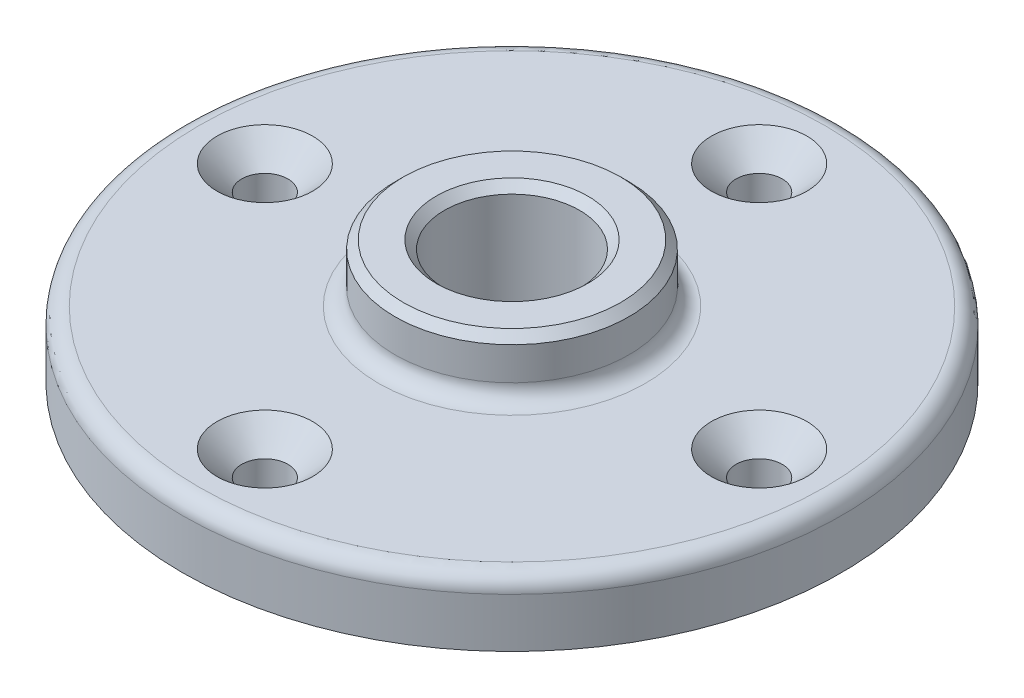
SolidWorks part; units mm, degrees
material "Nickel"
ref_plane "Front Plane" through (0, 0, 0) normal (0, 0, 1) x (1, 0, 0)
ref_plane "Top Plane" through (0, 0, 0) normal (0, 1, 0) x (1, 0, 0)
ref_plane "Right Plane" through (0, 0, 0) normal (1, 0, 0) x (0, 0, -1)
sketch "Sketch1" plane through (0, 0, 0) normal (0, 1, 0) x (1, 0, 0)
  circle A0 centre (0, 0) radius 20
  dimension "D1" = 40
extrude "Boss-Extrude1" add sketch "Sketch1" along normal blind 4
sketch "Sketch2" plane through (0, 4, 0) normal (0, 1, 0) x (1, 0, 0)
  circle A0 centre (0, 0) radius 4.1
  dimension "D1" = 8.2
extrude "Cut-Extrude1" cut sketch "Sketch2" against normal through all
sketch "Sketch3" plane through (0, 4, 0) normal (0, 1, 0) x (1, 0, 0)
  line L0 (0, 20) -> (0, 0) construction
  circle A0 centre (0, 0) radius 20 construction
  circle A1 centre (0, 15) radius 1.4
  dimension "D2" = 2.8
  dimension "D1" = 15
extrude "Cut-Extrude2" cut sketch "Sketch3" against normal through all
chamfer "Chamfer1" distance 1.5 angle 45 1 edges at (0, 4, -13.6)
ref_axis "Axis1" through (0, 0, 0) along (0, 1, 0)
pattern_circular "CirPattern1" count 4 over 360 about axis through (0, 0, 0) along (0, 1, 0) of "Cut-Extrude2", "Chamfer1"
fillet "Fillet1" radius 1 1 edges at (0, 4, 20)
sketch "Sketch4" plane through (0, 4, 0) normal (0, 1, 0) x (1, 0, 0)
  circle A0 centre (0, 0) radius 4.1 construction
  circle A1 centre (0, 0) radius 4.1
  circle A2 centre (0, 0) radius 7.1
  dimension "D1" = 3
extrude "Boss-Extrude2" add sketch "Sketch4" along normal blind 3.5
chamfer "Chamfer2" distance 0.5 angle 45 1 edges at (0, 7.5, 4.1)
fillet "Fillet2" radius 1 1 edges at (0, 4, 7.1)
chamfer "Chamfer3" distance 0.5 angle 45 1 edges at (0, 7.5, 7.1)
